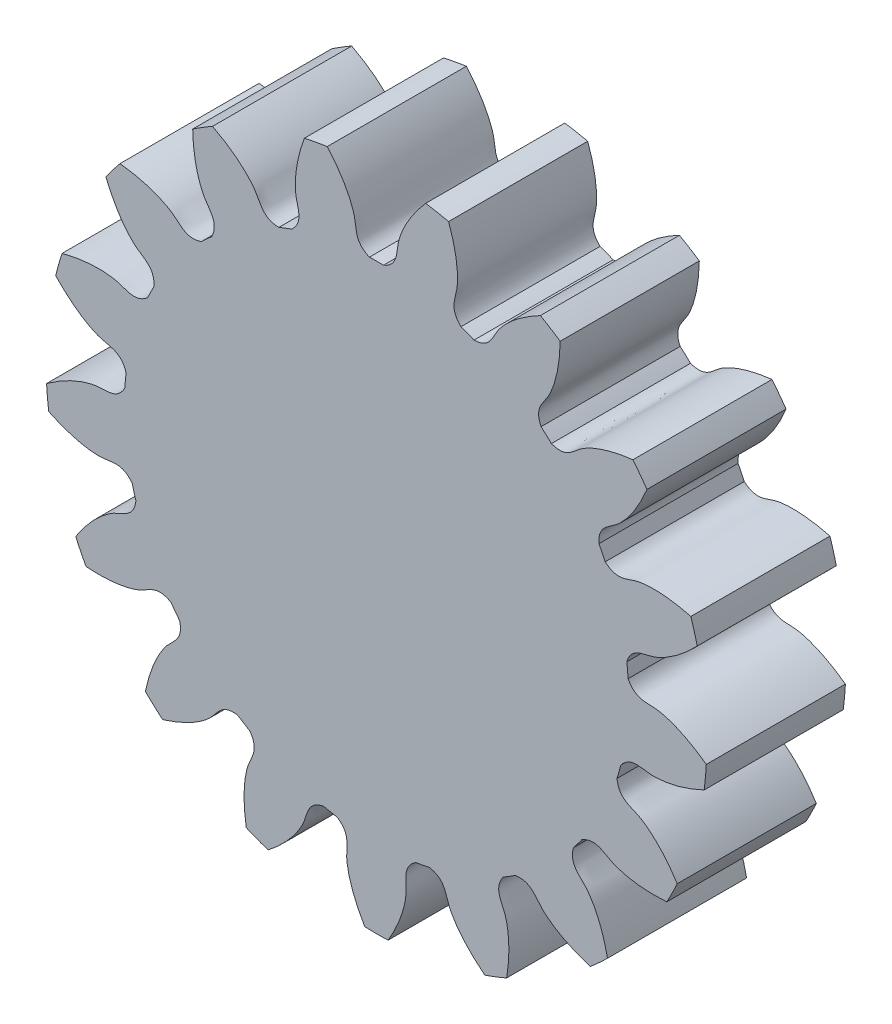
SolidWorks part; units mm, degrees
ref_plane "前视基准面" through (0, 0, 0) normal (0, 0, 1) x (1, 0, 0)
ref_plane "上视基准面" through (0, 0, 0) normal (0, 1, 0) x (1, 0, 0)
ref_plane "右视基准面" through (0, 0, 0) normal (1, 0, 0) x (0, 0, -1)
sketch "草图1" plane through (0, 0, 0) normal (0, 0, 1) x (1, 0, 0)
  circle A0 centre (0, 0) radius 9.5
extrude "凸台-拉伸1" add sketch "草图1" along normal blind 4
ref_axis "基准轴1" through (0, 0, -1.5) along (0, 0, 1)
sketch "草图2" plane through (0, 0, 0) normal (0, 0, 1) x (1, 0, 0)
  line L0 (0, 0) -> (0, 9.5) construction
  circle A0 centre (0, 0) radius 9.5 construction
  arc A1 (0.2017, 7.2472) -> (-0.2017, 7.2472) centre (0, 0) ccw
  arc A2 (3.1156, 10.7407) -> (-3.1156, 10.7407) centre (0, 0) ccw
  spline S0 degree 3 poles (0.2017, 7.2472) (0.6279, 7.4248) (0.5662, 7.7548) (0.6383, 8.0648) (0.645, 8.0912) (0.653, 8.1204) (0.6626, 8.1526) (0.6737, 8.1876) (0.6866, 8.2254) (0.7013, 8.266) (0.7179, 8.3092) (0.7367, 8.355) (0.7576, 8.4034) (0.7808, 8.4543) (0.8064, 8.5076) (0.8345, 8.5632) (0.8652, 8.621) (0.8986, 8.6811) (0.9348, 8.7432) (0.9739, 8.8073) (1.016, 8.8733) (1.0612, 8.9411) (1.1095, 9.0106) (1.1612, 9.0817) (1.2161, 9.1543) (1.2745, 9.2283) (1.3363, 9.3036) (1.4018, 9.3801) (1.4709, 9.4576) (1.5436, 9.5361) (1.6202, 9.6154) (1.7006, 9.6954) (1.7849, 9.776) (1.8731, 9.8571) (1.9653, 9.9385) (2.0616, 10.0201) (2.162, 10.1017) (2.2665, 10.1833) (2.3752, 10.2648) (2.488, 10.3459) (2.6051, 10.4265) (2.7265, 10.5066) (2.8958, 10.6134) (3.0266, 10.6905) (3.1156, 10.7407) knots 0 0 0 0 0.193883 0.199024 0.204851 0.211363 0.21856 0.226443 0.235011 0.244265 0.254205 0.264829 0.27614 0.288136 0.300817 0.314184 0.328236 0.342973 0.358397 0.374505 0.391299 0.408779 0.426944 0.445795 0.465331 0.485552 0.506459 0.528051 0.550329 0.573293 0.596941 0.621276 0.646296 0.672001 0.698392 0.725468 0.753229 0.781677 0.810809 0.840627 0.871131 0.90232 0.934195 1 1 1 1
  spline S1 degree 3 poles (-0.2017, 7.2472) (-0.6279, 7.4248) (-0.5662, 7.7548) (-0.6383, 8.0648) (-0.645, 8.0912) (-0.653, 8.1204) (-0.6626, 8.1526) (-0.6737, 8.1876) (-0.6866, 8.2254) (-0.7013, 8.266) (-0.7179, 8.3092) (-0.7367, 8.355) (-0.7576, 8.4034) (-0.7808, 8.4543) (-0.8064, 8.5076) (-0.8345, 8.5632) (-0.8652, 8.621) (-0.8986, 8.6811) (-0.9348, 8.7432) (-0.9739, 8.8073) (-1.016, 8.8733) (-1.0612, 8.9411) (-1.1095, 9.0106) (-1.1612, 9.0817) (-1.2161, 9.1543) (-1.2745, 9.2283) (-1.3363, 9.3036) (-1.4018, 9.3801) (-1.4709, 9.4576) (-1.5436, 9.5361) (-1.6202, 9.6154) (-1.7006, 9.6954) (-1.7849, 9.776) (-1.8731, 9.8571) (-1.9653, 9.9385) (-2.0616, 10.0201) (-2.162, 10.1017) (-2.2665, 10.1833) (-2.3752, 10.2648) (-2.488, 10.3459) (-2.6051, 10.4265) (-2.7265, 10.5066) (-2.8958, 10.6134) (-3.0266, 10.6905) (-3.1156, 10.7407) knots 0 0 0 0 0.193883 0.199024 0.204851 0.211363 0.21856 0.226443 0.235011 0.244265 0.254205 0.264829 0.27614 0.288136 0.300817 0.314184 0.328236 0.342973 0.358397 0.374505 0.391299 0.408779 0.426944 0.445795 0.465331 0.485552 0.506459 0.528051 0.550329 0.573293 0.596941 0.621276 0.646296 0.672001 0.698392 0.725468 0.753229 0.781677 0.810809 0.840627 0.871131 0.90232 0.934195 1 1 1 1
extrude "切除-拉伸1" cut sketch "草图2" along normal through all
pattern_circular "阵列(圆周)1" count 17 every 21.176 about axis through (0, 0, -1.5) along (0, 0, 1) of "切除-拉伸1"
sketch "草图3" plane through (0, 0, 0) normal (0, 0, 1) x (1, 0, 0)
  circle A0 centre (0, 0) radius 8.5 construction
  dimension "Dn" = 17
